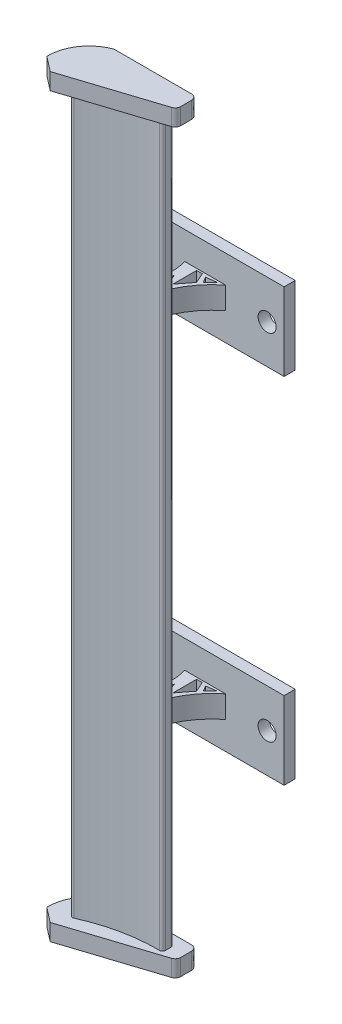
SolidWorks part; units mm, degrees
ref_plane "Alzado" through (0, 0, 0) normal (0, 0, 1) x (1, 0, 0)
ref_plane "Planta" through (0, 0, 0) normal (0, 1, 0) x (1, 0, 0)
ref_plane "Vista lateral" through (0, 0, 0) normal (1, 0, 0) x (0, 0, -1)
sketch "Croquis1" plane through (0, 0, 0) normal (0, 0, 1) x (1, 0, 0)
  line L0 (-12.55, -63.7963) -> (-14.55, -63.7963) construction
  line L1 (12.55, -49.7963) -> (14.55, -49.7963) construction
  line L2 (-12.55, 14) -> (-14.55, 14) construction
  line L3 (14.55, -49.7963) -> (-14.55, -49.7963)
  line L4 (14.55, -49.7963) -> (14.55, -63.7963)
  line L5 (14.55, -63.7963) -> (-14.55, -63.7963)
  line L6 (-14.55, -49.7963) -> (-14.55, -63.7963)
  line L7 (12.55, 0) -> (14.55, 0) construction
  line L9 (14.55, 0) -> (-14.55, 0)
  line L10 (14.55, 0) -> (14.55, 14)
  line L11 (14.55, 14) -> (-14.55, 14)
  line L12 (-14.55, 0) -> (-14.55, 14)
  circle A0 centre (11.49, -56.7964) radius 1.625
  circle A1 centre (-11.5, -56.7963) radius 1.625
  circle A2 centre (-11.5, 7) radius 1.625
  circle A3 centre (11.49, 7) radius 1.625
  dimension "D1" = 3.25
  dimension "D2" = 29.1
  dimension "D3" = 2
extrude "Saliente-Extruir1" add sketch "Croquis1" along normal blind 2
sketch "Croquis2" plane through (0, 0, 2) normal (0, 0, 1) x (1, 0, 0)
  line L0 (9.865, 7) -> (-9.875, 7) construction
  line L1 (9.865, -56.7964) -> (-9.875, -56.7964) construction
  line L2 (-0.005, 7) -> (-0.005, 11) construction
  line L3 (-0.005, 7) -> (-0.005, 3) construction
  line L4 (-0.005, 3) -> (3.995, 3) construction
  line L5 (3.995, 3) -> (3.995, 11) construction
  line L6 (3.995, 11) -> (-4.005, 11) construction
  line L8 (-4.005, 11) -> (3.995, 11)
  line L9 (-4.005, 11) -> (-4.005, 3)
  line L10 (-4.005, 3) -> (3.995, 3)
  line L11 (3.995, 11) -> (3.995, 3)
  line L13 (-4.005, -56.7964) -> (-4.005, -60.7964) construction
  line L14 (-4.005, -60.7964) -> (3.995, -60.7964) construction
  line L15 (3.995, -60.7964) -> (3.995, -52.7964) construction
  line L16 (-14.55, 14) -> (-14.55, 0) construction
  line L17 (-4.005, -60.7964) -> (3.995, -60.7964)
  line L18 (-4.005, -60.7964) -> (-4.005, -52.7964)
  line L19 (-4.005, -52.7964) -> (3.995, -52.7964)
  line L20 (3.995, -60.7964) -> (3.995, -52.7964)
  circle A0 centre (11.49, 7) radius 1.625 construction
  circle A1 centre (-11.5, 7) radius 1.625 construction
  circle A2 centre (11.49, -56.7964) radius 1.625 construction
  circle A3 centre (-11.5, -56.7963) radius 1.625 construction
  dimension "D1" = 10.545
extrude "Saliente-Extruir2" add sketch "Croquis2" along normal blind 7
sketch "Croquis3" plane through (0, 0, 9) normal (0, 0, 1) x (1, 0, 0)
  line L0 (3.995, 11) -> (13.995, 11) construction
  line L1 (13.995, 11) -> (13.995, 43) construction
  line L2 (-4.005, -60.7964) -> (-14.005, -60.7964) construction
  line L3 (-14.005, -60.7964) -> (-14.005, -92.7964) construction
  line L4 (3.995, 3) -> (3.995, 11) construction
  line L5 (13.995, 43) -> (-14.005, 43)
  line L6 (13.995, 43) -> (13.995, -92.7964)
  line L7 (13.995, -92.7964) -> (-14.005, -92.7964)
  line L8 (-14.005, 43) -> (-14.005, -92.7964)
  line L9 (3.995, 11) -> (-4.005, 11) construction
  dimension "D1" = 10
  dimension "D2" = 32
extrude "Saliente-Extruir3" add sketch "Croquis3" along normal blind 8
sketch "Croquis4" plane through (0, 43, 0) normal (0, 1, 0) x (1, 0, 0)
  line L2 (3.995, -9) -> (3.995, -11)
  line L5 (-4.005, -9) -> (-4.005, -11)
  line L6 (-4.005, -11) -> (-7.005, -11)
  line L7 (-0.005, -17) -> (-0.005, -9) construction
  line L8 (13.995, -17) -> (-14.005, -17) construction
  line L9 (13.995, -9) -> (-14.005, -9) construction
  line L10 (-0.005, -13) -> (6.995, -13) construction
  line L11 (-0.005, -13) -> (-7.005, -13) construction
  line L12 (-7.005, -13) -> (-7.005, -16)
  line L13 (-7.005, -13) -> (-7.005, -11)
  line L14 (6.995, -13) -> (6.995, -11)
  line L15 (6.995, -11) -> (3.995, -11)
  line L16 (-14.005, -17) -> (-14.005, -9) construction
  line L17 (13.995, -17) -> (-14.005, -17)
  line L18 (13.995, -17) -> (13.995, -9)
  line L19 (13.995, -9) -> (3.995, -9)
  line L20 (-14.005, -17) -> (-14.005, -9)
  line L21 (-4.005, -9) -> (-14.005, -9)
  arc A2 (6.995, -13) -> (-7.005, -16) centre (6.0993, -42.9866) ccw
  dimension "D1" = 30
  dimension "D2" = 7
  dimension "D3" = 20.1043
  dimension "D4" = 2
extrude "Cortar-Extruir1" cut sketch "Croquis4" against normal up to vertex (135.7963 mm away) up to point (13.995, -92.7964, 17)
fillet "Redondeo1" radius 0.5 2 edges at (6.995, -24.8982, 11) (6.995, -24.8982, 13)
fillet "Redondeo2" radius 0.5 1 edges at (-7.005, -24.8982, 16)
sketch "Croquis5" plane through (-4.005, 0, 0) normal (-1, 0, 0) x (0, 0, 1)
  line L0 (9, -52.7964) -> (11, -52.7964) construction
  line L1 (11, 43) -> (9, 43)
  line L2 (11, 43) -> (11, 11)
  line L3 (11, 11) -> (9, 11)
  line L4 (9, 43) -> (9, 11)
  line L6 (11, 43) -> (9, 43) construction
  line L7 (9, 3) -> (11, 3)
  line L8 (9, 3) -> (9, -52.7964)
  line L9 (9, -52.7964) -> (11, -52.7964)
  line L10 (11, 3) -> (11, -52.7964)
  line L11 (9, -60.7964) -> (11, -60.7964)
  line L12 (9, -60.7964) -> (9, -92.7964)
  line L13 (9, -92.7964) -> (11, -92.7964)
  line L14 (11, -60.7964) -> (11, -92.7964)
  line L15 (11, -92.7964) -> (11, 43) construction
  dimension "D1" = 2
  dimension "D2" = 32
  dimension "D3" = 40
  dimension "D4" = 95.7964
  dimension "D5" = 103.7964
extrude "Cortar-Extruir2" cut sketch "Croquis5" against normal up to vertex (8 mm away) up to point (3.995, -92.7964, 9)
sketch "Croquis6" plane through (0, 43, 0) normal (0, 1, 0) x (1, 0, 0)
  line L0 (9.4573, -12.9083) -> (-7.7592, -18.4742)
  line L7 (-5.505, -9.2292) -> (9.4573, -9.2292)
  line L8 (9.4573, -12.9083) -> (9.4573, -9.2292)
  line L9 (-7.7592, -18.4742) -> (-10.4478, -16.3988)
  line L10 (-7.005, -11.5) -> (-5.505, -11.5) construction
  line L11 (-5.505, -11.5) -> (-5.505, -9.2292) construction
  line L14 (-7.005, -15.2129) -> (-7.005, -11) construction
  line L15 (-7.005, -11) -> (6.495, -11) construction
  arc A0 (-5.505, -9.2292) -> (-10.4478, -16.3988) centre (-2.9487, -16.2801) ccw
  dimension "D1" = 7.5
  dimension "D2" = 1.5
  dimension "D3" = 4.0563
  dimension "D4" = 16.4623
  dimension "D5" = 0.7542
  dimension "D6" = 3.4428
  dimension "D7" = 1.7708
  dimension "D8" = 0.5
  dimension "D9" = 1.9083
  dimension "D12" = 7.4742
extrude "Saliente-Extruir4" add sketch "Croquis6" against normal blind 3
fillet "Redondeo4" radius 1 2 edges at (9.4573, 41.5, 9.2292) (9.4573, 41.5, 12.9083)
sketch "Croquis7" plane through (0, -92.7964, 0) normal (0, -1, 0) x (1, 0, 0)
  line L0 (-7.7592, 18.4742) -> (8.7649, 13.1321)
  line L1 (9.4573, 12.1806) -> (9.4573, 10.2292)
  line L2 (8.4573, 9.2292) -> (-5.505, 9.2292)
  line L3 (-7.7592, 18.4742) -> (-10.4478, 16.3988)
  arc A0 (-10.4478, 16.3988) -> (-5.505, 9.2292) centre (-2.9487, 16.2801) ccw
  arc A1 (8.7649, 13.1321) -> (9.4573, 12.1806) centre (8.4573, 12.1806) cw
  arc A2 (9.4573, 10.2292) -> (8.4573, 9.2292) centre (8.4573, 10.2292) cw
  dimension "D1" = 7.5
extrude "Saliente-Extruir5" add sketch "Croquis7" against normal blind 3
sketch "Croquis11" plane through (0, 11, 0) normal (0, 1, 0) x (1, 0, 0)
  line L0 (14.55, -2) -> (-14.55, -2) construction
  line L1 (-4.005, -11) -> (-3.005, -11)
  line L2 (3.995, -11) -> (1.995, -11)
  line L3 (3.995, -11) -> (-4.005, -11) construction
  line L4 (3.995, -11) -> (3.995, -5.7563)
  line L5 (-4.005, -11) -> (-4.005, -2)
  line L6 (-4.005, -2) -> (0, -2)
  line L7 (-4.005, -11) -> (-4.005, -2) construction
  arc A0 (1.995, -11) -> (3.995, -5.7563) centre (16.4558, -13.5122) cw
  arc A1 (-3.005, -11) -> (0, -2) centre (-7.6124, -4.46) ccw
  dimension "D1" = 14.6774
  dimension "D2" = 8
  dimension "D3" = 6
  dimension "D4" = 20.4608
extrude "Cortar-Extruir4" cut sketch "Croquis11" against normal up to vertex (71.7964 mm away) up to point (3.995, -60.7964, 11)
sketch "Croquis12" plane through (0, 11, 0) normal (0, 1, 0) x (1, 0, 0)
  line L0 (3.995, -2) -> (7.3511, -2)
  line L3 (3.995, -5.7563) -> (3.995, -2)
  arc A0 (7.3511, -2) -> (3.995, -5.7563) centre (16.4558, -13.5122) ccw
extrude "Saliente-Extruir7" add sketch "Croquis12" against normal up to vertex (8 mm away) up to point (3.995, 3, 5.7563)
sketch "Croquis13" plane through (0, -60.7964, 0) normal (0, -1, 0) x (1, 0, 0)
  line L0 (3.995, 5.7563) -> (3.995, 2)
  line L1 (3.995, 2) -> (7.3511, 2)
  arc A0 (3.995, 5.7563) -> (7.3511, 2) centre (16.4558, 13.5122) ccw
extrude "Saliente-Extruir8" add sketch "Croquis13" against normal up to vertex (8 mm away) up to point (3.995, -52.7964, 2)
sketch "Croquis14" plane through (0, 11, 0) normal (0, 1, 0) x (1, 0, 0)
  line L3 (6.2169, -2.3247) -> (4.9277, -3.5656)
  line L4 (4.9277, -3.5656) -> (4.3314, -2.5664)
  line L5 (4.3314, -2.5664) -> (6.2169, -2.3247)
  line L6 (3.4933, -2.3247) -> (2.478, -2.3247)
  line L7 (2.478, -2.3247) -> (2.478, -6.5954)
  line L8 (2.478, -6.5954) -> (4.3314, -4.2102)
  line L9 (4.3314, -4.2102) -> (3.4933, -2.3247)
  line L10 (1.2353, -5.0759) -> (2.0027, -7.1671)
  line L11 (2.0027, -7.1671) -> (1.2353, -8.4908)
  line L12 (1.2353, -8.4908) -> (0.1609, -8.6827)
  line L13 (0.1609, -8.6827) -> (1.2353, -5.0759)
  line L14 (0.9716, -10.5152) -> (-1.5314, -10.5152)
  line L15 (-1.5314, -10.5152) -> (1.2353, -9.2573)
  line L16 (1.2353, -9.2573) -> (0.9716, -10.5152)
  line L17 (7.3511, -2) -> (0, -2) construction
  dimension "D1" = 1.1342
  dimension "D2" = 2.4235
  dimension "D3" = 3.0198
  dimension "D4" = 3.8578
  dimension "D5" = 4.8731
  dimension "D6" = 5.3485
  dimension "D7" = 6.1159
  dimension "D8" = 6.3796
  dimension "D9" = 7.1902
  dimension "D10" = 8.8825
  dimension "D11" = 0.3247
  dimension "D12" = 0.5664
  dimension "D13" = 1.5656
  dimension "D14" = 2.2102
  dimension "D15" = 3.0759
  dimension "D16" = 4.5954
  dimension "D17" = 5.1671
  dimension "D18" = 6.4908
  dimension "D19" = 6.6827
  dimension "D20" = 7.2573
  dimension "D21" = 8.5152
extrude "Cortar-Extruir5" cut sketch "Croquis14" against normal up to vertex (71.7964 mm away) up to point (1.995, -60.7964, 11)
fillet "Redondeo5" radius 4 1 edges at (-7.005, -24.8982, 11)
sketch "Croquis15" plane through (-14.55, 0, 0) normal (-1, 0, 0) x (0, 0, 1)
  line L1 (11, -60.7964) -> (11, -52.7964) construction
  line L2 (2, 14) -> (2, 0) construction
  line L3 (11, 11) -> (2, 11)
  line L4 (11, 11) -> (11, 9)
  line L5 (11, 9) -> (2, 9)
  line L6 (2, 11) -> (2, 9)
  line L7 (11, -54.7964) -> (11, -56.7964) construction
  line L8 (11, 5) -> (2, 5)
  line L9 (11, 5) -> (11, 3)
  line L10 (11, 3) -> (2, 3)
  line L11 (2, 5) -> (2, 3)
  line L12 (11, -56.7964) -> (11, -58.7964) construction
  line L13 (11, -54.7964) -> (2, -54.7964)
  line L14 (11, -54.7964) -> (11, -52.7964)
  line L15 (11, -52.7964) -> (2, -52.7964)
  line L16 (2, -54.7964) -> (2, -52.7964)
  line L17 (11, -58.7964) -> (2, -58.7964)
  line L18 (11, -58.7964) -> (11, -60.7964)
  line L19 (11, -60.7964) -> (2, -60.7964)
  line L20 (2, -58.7964) -> (2, -60.7964)
extrude "Cortar-Extruir6" cut sketch "Croquis15" against normal up to vertex (21.9011 mm away) up to point (7.3511, -52.7964, 2)
sketch "Croquis16" plane through (0, 14, 0) normal (0, 1, 0) x (1, 0, 0)
  line L0 (14.55, -2) -> (-14.55, -2) construction
  line L1 (14.55, 0) -> (8.7794, 0)
  line L2 (14.55, 0) -> (14.55, -2)
  line L3 (14.55, -2) -> (8.7794, -2)
  line L4 (8.7794, 0) -> (8.7794, -2)
  line L5 (14.55, 0) -> (-14.55, 0) construction
  line L6 (-14.55, -2) -> (-1.7979, -2)
  line L7 (-14.55, -2) -> (-14.55, 0)
  line L8 (-14.55, 0) -> (-1.7979, 0)
  line L9 (-1.7979, -2) -> (-1.7979, 0)
  line L10 (-14.55, -2) -> (-14.55, 0) construction
  dimension "D1" = 12.7521
  dimension "D2" = 23.3294
extrude "Cortar-Extruir7" cut sketch "Croquis16" against normal up to vertex (77.7964 mm away) up to point (-14.55, -63.7963, 2)
sketch "Croquis17" plane through (0, 0, 2) normal (0, 0, 1) x (1, 0, 0)
  line L0 (-11.1882, 12) -> (-11.1882, 14) construction
  line L1 (8.7794, 14) -> (17.9118, 14)
  line L2 (8.7794, 14) -> (8.7794, 0)
  line L3 (8.7794, 0) -> (17.9118, 0)
  line L4 (17.9118, 14) -> (17.9118, 0)
  line L5 (-1.7979, 0) -> (-1.7979, 14) construction
  line L6 (-11.1882, -61.7963) -> (-11.1882, -63.7963) construction
  line L7 (-11.1882, -63.7963) -> (-9.1882, -63.7963) construction
  line L8 (-1.7979, 0) -> (-11.1882, 0)
  line L9 (-1.7979, 0) -> (-1.7979, 14)
  line L10 (-1.7979, 14) -> (-11.1882, 14)
  line L11 (-11.1882, 0) -> (-11.1882, 14)
  line L12 (-1.7979, -49.7963) -> (-11.1882, -49.7963)
  line L13 (-1.7979, -49.7963) -> (-1.7979, -63.7963)
  line L14 (-1.7979, -63.7963) -> (-11.1882, -63.7963)
  line L15 (-11.1882, -49.7963) -> (-11.1882, -63.7963)
  line L16 (17.9118, -49.7963) -> (8.7794, -49.7963)
  line L17 (17.9118, -49.7963) -> (17.9118, -63.7963)
  line L18 (17.9118, -63.7963) -> (8.7794, -63.7963)
  line L19 (8.7794, -49.7963) -> (8.7794, -63.7963)
  line L20 (8.7794, 14) -> (-1.7979, 14) construction
  circle A0 centre (14.8518, 7) radius 1.625
  circle A1 centre (14.8518, -56.7963) radius 1.625
  circle A2 centre (-8.1382, -56.7963) radius 1.625
  circle A3 centre (-8.1382, 7) radius 1.625
  dimension "D1" = 3.25
  dimension "D2" = 19.7097
extrude "Saliente-Extruir9" add sketch "Croquis17" against normal up to vertex (2 mm away) up to point (8.7794, 0, 0)
